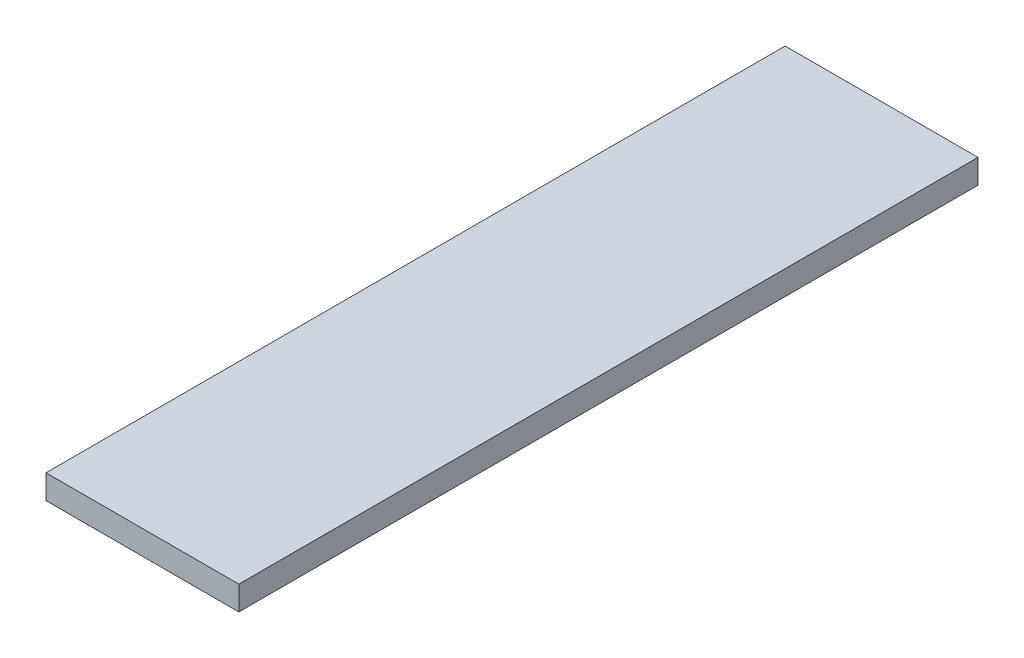
SolidWorks part; units mm, degrees
material "Cedar"
ref_plane "Front Plane" through (0, 0, 0) normal (0, 0, 1) x (1, 0, 0)
ref_plane "Top Plane" through (0, 0, 0) normal (0, 1, 0) x (1, 0, 0)
ref_plane "Right Plane" through (0, 0, 0) normal (1, 0, 0) x (0, 0, -1)
sketch "Sketch1" plane through (0, 0, 0) normal (0, 1, 0) x (1, 0, 0)
  line L1 (0, 0) -> (152.4, 0)
  line L2 (0, 0) -> (0, 584.2)
  line L3 (0, 584.2) -> (152.4, 584.2)
  line L4 (152.4, 0) -> (152.4, 584.2)
  dimension "D1" = 584.2
  dimension "D2" = 152.4
extrude "Boss-Extrude1" add sketch "Sketch1" along normal blind 19.05
